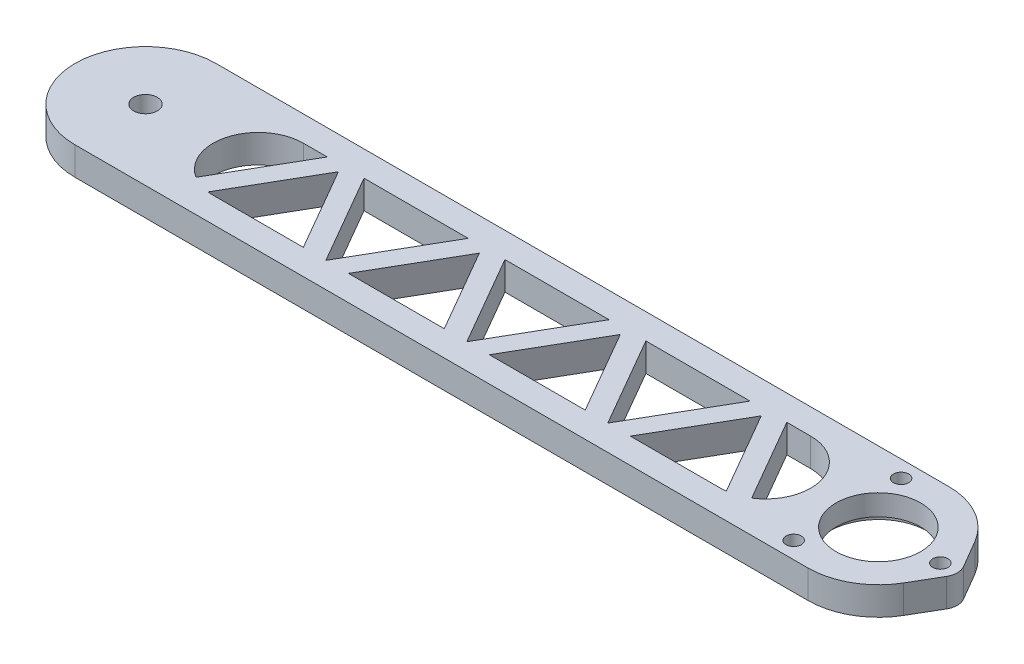
SolidWorks part; units mm, degrees
ref_plane "前视基准面" through (0, 0, 0) normal (0, 0, 1) x (1, 0, 0)
ref_plane "上视基准面" through (0, 0, 0) normal (0, 1, 0) x (1, 0, 0)
ref_plane "右视基准面" through (0, 0, 0) normal (1, 0, 0) x (0, 0, -1)
sketch "草图1" plane through (0, 0, 0) normal (0, 1, 0) x (1, 0, 0)
  line L0 (-65, 0) -> (65, 0) construction
  line L1 (-65, 12.5) -> (65, 12.5)
  line L2 (-65, -12.5) -> (65, -12.5)
  arc A0 (-65, 12.5) -> (-65, -12.5) centre (-65, 0) ccw
  arc A1 (65, -12.5) -> (65, 12.5) centre (65, 0) ccw
  point P2 (0, 0)
  dimension "D2" = 12.5
  dimension "D1" = 130
extrude "凸台-拉伸1" add sketch "草图1" along normal blind 5
sketch "草图10" plane through (0, 0, 0) normal (0, -1, 0) x (1, 0, 0)
  line L0 (75.7955, -6.3014) -> (78.5909, -1.5123)
  line L3 (75.7955, 6.3014) -> (78.5909, 1.5123)
  line L4 (75.7955, -6.3014) -> (75.7955, 6.3014)
  line L5 (76, 0) -> (77.5, 0) construction
  circle A5 centre (76, 0) radius 3 construction
  arc A6 (65, -12.5) -> (65, 12.5) centre (65, 0) ccw construction
  arc A7 (78.5909, -1.5123) -> (78.5909, 1.5123) centre (76, 0) ccw
  dimension "D1" = 6
  dimension "D2" = 1.5
extrude "凸台-拉伸5" add sketch "草图10" against normal up to surface (5 mm away) up to face at (0, 5, 0)
sketch "草图7" plane through (0, 5, 0) normal (0, 1, 0) x (1, 0, 0)
  circle A0 centre (65, 0) radius 7.5
  dimension "D1" = 15
extrude "切除-拉伸2" cut sketch "草图7" against normal up to next
sketch "草图8" plane through (0, 0, 0) normal (0, 1, 0) x (1, 0, 0)
  circle A0 centre (65, 0) radius 8.75
  dimension "D1" = 17.5
extrude "切除-拉伸3" cut sketch "草图8" along normal blind 1.3
sketch "草图9" plane through (0, 0, 0) normal (0, -1, 0) x (1, 0, 0)
  line L0 (65, 0) -> (54, 0) construction
  line L1 (65, 0) -> (59.5, 9.5263) construction
  circle A0 centre (65, 0) radius 11 construction
  circle A5 centre (59.5, 9.5263) radius 1.35
  circle A9 centre (76, 0) radius 1.35
  circle A10 centre (59.5, -9.5263) radius 1.35
  point P12 (65, 0)
  point P15 (65, 0)
  dimension "22" = 22
  dimension "D3" = 2.7
  dimension "D2" = 60
  dimension "D1" = 3
extrude "切除-拉伸4" cut sketch "草图9" against normal up to next
sketch "草图12" plane through (0, 5, 0) normal (0, 1, 0) x (1, 0, 0)
  circle A0 centre (-65, 0) radius 2.1
  dimension "D1" = 4.2
extrude "切除-拉伸5" cut sketch "草图12" against normal up to next
sketch "草图13" plane through (0, 5, 0) normal (0, 1, 0) x (1, 0, 0)
  line L0 (-45, 0) -> (45, 0) construction
  line L1 (-45, 8) -> (45, 8)
  line L2 (-45, -8) -> (45, -8)
  arc A0 (-45, 8) -> (-45, -8) centre (-45, 0) ccw
  arc A1 (45, -8) -> (45, 8) centre (45, 0) ccw
  point P2 (0, 0)
  dimension "D1" = 8
  dimension "D2" = 90
extrude "切除-拉伸6" cut sketch "草图13" against normal up to next
sketch "草图14" plane through (0, 5, 0) normal (0, 1, 0) x (1, 0, 0)
  line L5 (-45, -8) -> (45, -8) construction
  line L6 (45, 8) -> (-45, 8) construction
  line L7 (0, -8) -> (9.2376, 8)
  line L8 (9.2376, 8) -> (13.2376, 8)
  line L9 (13.2376, 8) -> (4, -8)
  line L10 (4, -8) -> (0, -8)
  dimension "D1" = 4
  dimension "D2" = 60
extrude "凸台-拉伸6" add sketch "草图14" against normal up to surface (5 mm away) up to face at (0, 0, 0)
pattern_linear "阵列(线性)1" count 3 spacing 25 along (-1, 0, 0) count 2 spacing 25 along (1, 0, 0) of "凸台-拉伸6" pattern seed only yes
mirror "镜向1" about plane through (0, 0, 0) normal (1, 0, 0) of "阵列(线性)1"
